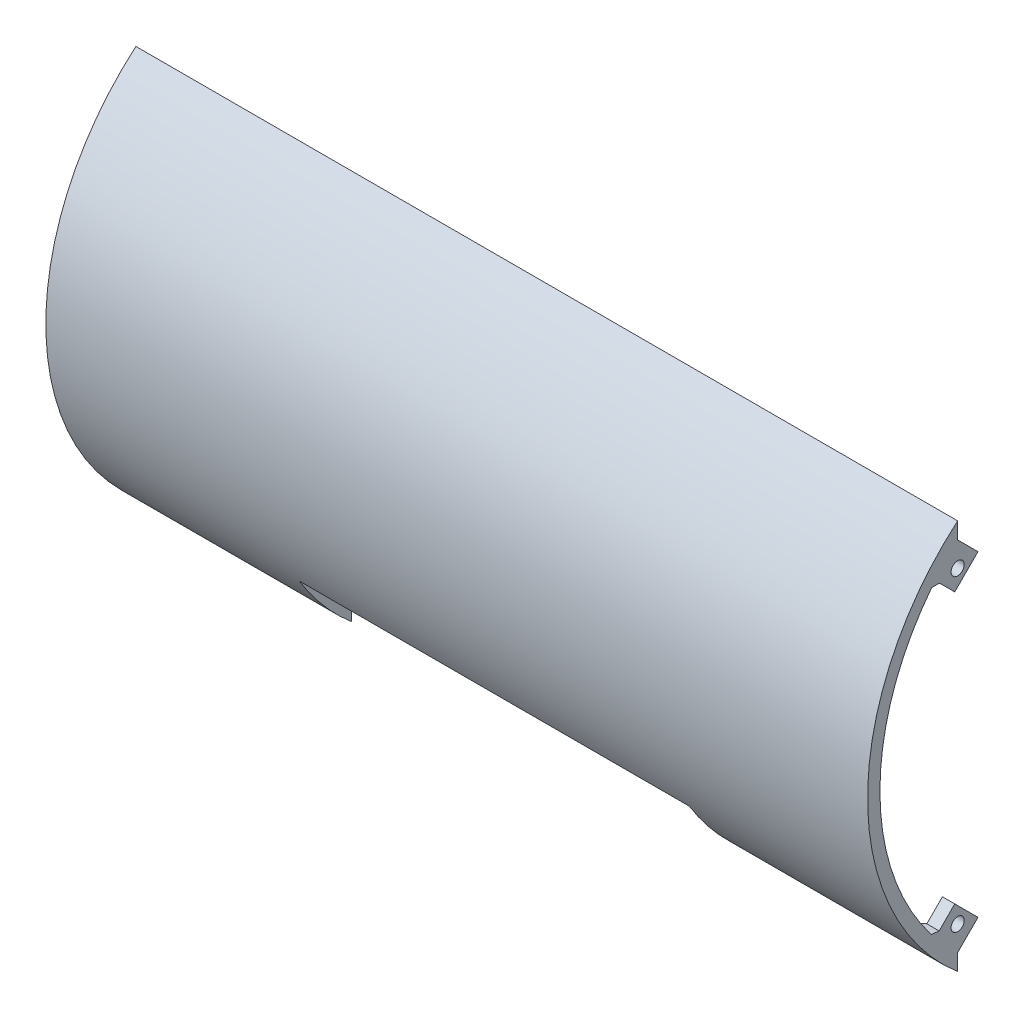
SolidWorks part; units mm, degrees
ref_plane "前视基准面" through (0, 0, 0) normal (0, 0, 1) x (1, 0, 0)
ref_plane "上视基准面" through (0, 0, 0) normal (0, 1, 0) x (1, 0, 0)
ref_plane "右视基准面" through (0, 0, 0) normal (1, 0, 0) x (0, 0, -1)
sketch "草图2" plane through (0, 0, 0) normal (1, 0, 0) x (0, 0, -1)
  line L0 (0, 0) -> (-59.42, 0) construction
  line L1 (-40.497, 47.5) -> (40.497, 47.5)
  line L2 (-40.497, -47.5) -> (40.497, -47.5)
  line L3 (-40.497, 47.5) -> (-40.497, 43.4825)
  line L4 (-40.497, -47.5) -> (-40.497, -43.4825)
  circle A0 centre (0, 0) radius 62.42
  circle A1 centre (0, 0) radius 59.42
  dimension "D1" = 124.84
  dimension "D2" = 118.84
  dimension "D3" = 47.5
extrude "凸台-拉伸2" add sketch "草图2" along normal blind 200 contours A1 L3 A0 L4
sketch "草图3" plane through (200, 0, 0) normal (1, 0, 0) x (0, 0, -1)
  line L0 (-40.497, 43.4825) -> (-35.5472, 38.5328)
  line L1 (-35.5472, 38.5328) -> (-41.2041, 32.8759)
  line L2 (-41.2041, 32.8759) -> (-45.9735, 37.6453)
  arc A0 (-40.497, 43.4825) -> (-40.497, -43.4825) centre (0, 0) ccw construction
  arc A1 (-40.497, 43.4825) -> (-40.497, -43.4825) centre (0, 0) ccw
  circle A2 centre (-40.497, 37.5004) radius 1.6
  arc M3 (-40.497, -43.4825) -> (-40.497, 43.4825) centre (0, 0) cw
  dimension "D3" = 3.2
  dimension "D4" = 4.23
  dimension "D5" = 2.77
  dimension "D1" = 7
  dimension "D2" = 8
extrude "凸台-拉伸3" add sketch "草图3" against normal blind 3 contours L2 L1 L0 M3
mirror "镜向2" about plane through (0, 0, 0) normal (0, 1, 0) of "凸台-拉伸3"
ref_plane "基准面1" through (100, 0, 0) normal (1, 0, 0) x (0, 0, -1)
mirror "镜向3" about plane through (100, 0, 0) normal (1, 0, 0) of "镜向2", "凸台-拉伸3"
chamfer "倒角2" distance 1.5 angle 45 8 edges at (3, -40.6563, 43.3337) (1.5, -37.6453, 45.9735) (3, 40.6563, 43.3337) (1.5, 37.6453, 45.9735) (198.5, -37.6453, 45.9735) (197, -40.6563, 43.3337) (198.5, 37.6453, 45.9735) (197, 40.6563, 43.3337)
sketch "草图4" plane through (0, 0, 40.497) normal (0, 0, -1) x (-1, 0, 0)
  line L0 (-100, 14.78) -> (-100, -14.78) construction
  line L1 (-147.5, -47.5) -> (-52.5, -47.5)
  line L2 (-147.5, -47.5) -> (-147.5, -32.5)
  line L3 (-147.5, -32.5) -> (-52.5, -32.5)
  line L4 (-52.5, -47.5) -> (-52.5, -32.5)
  line L5 (-147.5, -47.5) -> (-52.5, -32.5) construction
  line L6 (-147.5, -32.5) -> (-52.5, -47.5) construction
  line L7 (-200, -47.5) -> (0, -47.5) construction
  point P0 (-100, -40)
  dimension "D1" = 0
  dimension "D2" = 15
  dimension "D3" = 95
extrude "切除-拉伸1" cut sketch "草图4" against normal up to next
